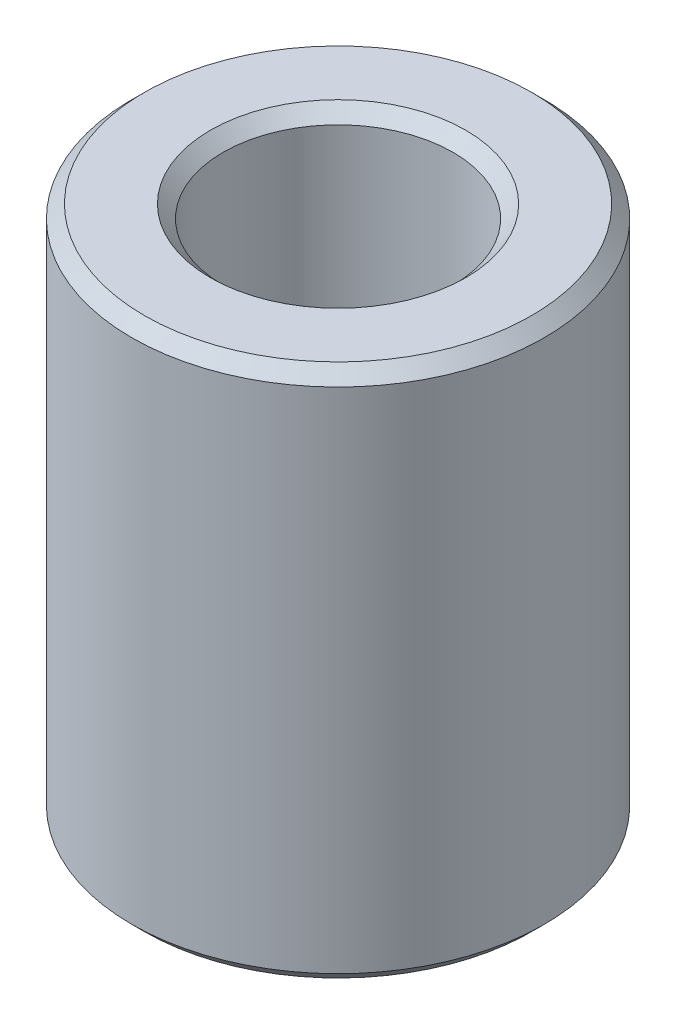
SolidWorks part; units mm, degrees
ref_plane "Front Plane" through (0, 0, 0) normal (0, 0, 1) x (1, 0, 0)
ref_plane "Top Plane" through (0, 0, 0) normal (0, 1, 0) x (1, 0, 0)
ref_plane "Right Plane" through (0, 0, 0) normal (1, 0, 0) x (0, 0, -1)
sketch "Sketch1" plane through (0, 0, 0) normal (0, 1, 0) x (1, 0, 0)
  circle A0 centre (0, 0) radius 52.5
  dimension "SLEEVE_OD" = 105
extrude "Boss-Extrude1" add sketch "Sketch1" along normal blind 135.8188
sketch "Sketch2" plane through (0, 0, 0) normal (0, 1, 0) x (1, 0, 0)
  circle A0 centre (0, 0) radius 29.2698
  dimension "BORE_D" = 58.5396
extrude "Cut-Extrude1" cut sketch "Sketch2" along normal through all
chamfer "Chamfer1" distance 3.2447 angle 45 4 edges at (0, 135.8188, 29.2698) (0, 0, 29.2698) (0, 0, 52.5) (0, 135.8188, 52.5)
